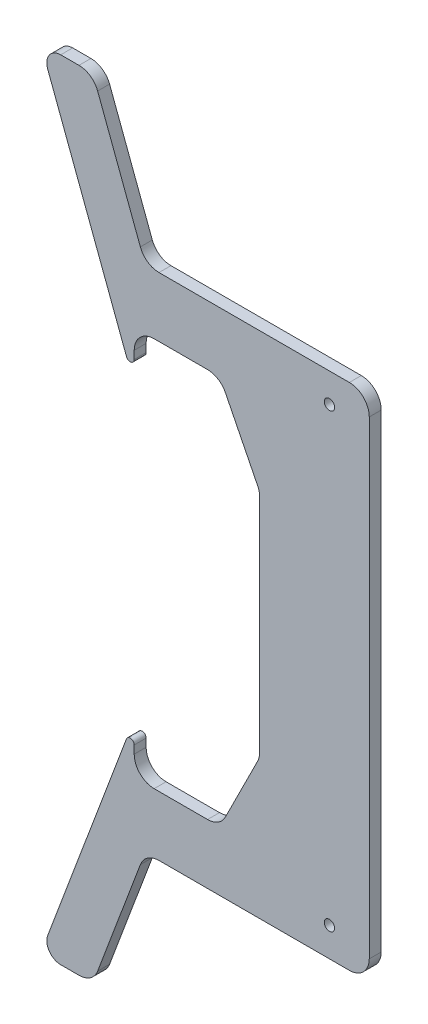
SolidWorks part; units mm, degrees
material "MDF"
ref_plane "Plano frontal" through (0, 0, 0) normal (0, 0, 1) x (1, 0, 0)
ref_plane "Plano superior" through (0, 0, 0) normal (0, 1, 0) x (1, 0, 0)
ref_plane "Plano direito" through (0, 0, 0) normal (1, 0, 0) x (0, 0, -1)
sketch "Esboço1" plane through (0, 0, 0) normal (0, 0, 1) x (1, 0, 0)
  line L0 (-20, 127.8) -> (-100, 127.8)
  line L1 (-20, -127.8) -> (20, -127.8)
  line L2 (-20, -127.8) -> (-20, 127.8)
  line L3 (-20, 127.8) -> (20, 127.8)
  line L4 (20, -127.8) -> (20, 127.8)
  line L5 (-20, -127.8) -> (20, 127.8) construction
  line L6 (-20, 127.8) -> (20, -127.8) construction
  line L7 (0, 0) -> (20, 0) construction
  line L8 (-145, 197.8) -> (-98, 72.8)
  line L9 (-98, 72.8) -> (-20, 72.8)
  line L10 (-100, 127.8) -> (-100, 197.8)
  line L11 (-145, -197.8) -> (-98, -72.8)
  line L12 (-98, -72.8) -> (-20, -72.8)
  line L13 (-98, 72.8) -> (-98, 97.8)
  line L14 (-98, 97.8) -> (-20, 97.8)
  line L15 (-20, 97.8) -> (-20, 72.8)
  line L16 (-20, -97.8) -> (-20, -72.8)
  line L17 (-98, -72.8) -> (-98, -97.8)
  line L18 (-98, -97.8) -> (-20, -97.8)
  line L19 (-100, 197.8) -> (-145, 197.8)
  line L20 (-100, -197.8) -> (-145, -197.8)
  line L21 (-20, -127.8) -> (-100, -127.8)
  line L22 (-100, -127.8) -> (-100, -197.8)
  line L23 (-100, 147.8) -> (-92.48, 127.8)
  line L24 (-100, -147.8) -> (-92.48, -127.8)
  line L25 (-100, 147.8) -> (-118.8, 197.8)
  line L26 (-100, -147.8) -> (-118.8, -197.8)
  line L27 (-55, 97.8) -> (-35, 57.8)
  line L28 (-55, -97.8) -> (-35, -57.8)
  line L29 (-35, 57.8) -> (-35, -57.8)
  circle A1 centre (0, 113.2) radius 2.6
  circle A2 centre (0, -113.2) radius 2.6
  point P0 (0, 0)
  point P34 (0, 127.8)
  dimension "D2" = 14.6
  dimension "D3" = 5.2
  dimension "D1" = 255.6
  dimension "D4" = 40
  dimension "D5" = 125
  dimension "D6" = 78
  dimension "D7" = 80
  dimension "D8" = 125
  dimension "D9" = 55
  dimension "D10" = 25
  dimension "D11" = 50
  dimension "D13" = 70
  dimension "D14" = 75
  dimension "D15" = 15
extrude "Ressalto-extrusão1" add sketch "Esboço1" along normal blind 6 contours L1 L4 L3 L2 A1 A2 | L22 L24 L21 | L23 L10 L0 | L28 L18 L2 L12 | L28 L12 L2 | L10 L25 L19 L8 L13 L14 L2 L0 | L14 L27 L9 L2 | L26 L22 L21 L2 L18 L17 L11 L20 region at (-21.7678, 112.8, 0) region at (0, 0, 0) region at (-97.4933, 134.4667, 0) region at (-34.6014, 86.2058, 0) region at (-27.9899, 0, 0) region at (-34.6014, -86.2058, 0) region at (-56.24, -126.0322, 0) region at (-97.4933, -134.4667, 0)
fillet "Filete1" radius 2 2 edges at (-98, -72.8, 3) (-98, 72.8, 3)
fillet "Filete3" radius 10 12 edges at (-92.48, -127.8, 3) (-118.8, -197.8, 3) (-98, -97.8, 3) (20, -127.8, 3) (20, 127.8, 3) (-98, 97.8, 3) (-92.48, 127.8, 3) (-118.8, 197.8, 3) (-55, -97.8, 3) (-55, 97.8, 3) (-35, -57.8, 3) (-35, 57.8, 3)
fillet "Filete4" radius 7 2 edges at (-145, 197.8, 3) (-145, -197.8, 3)
